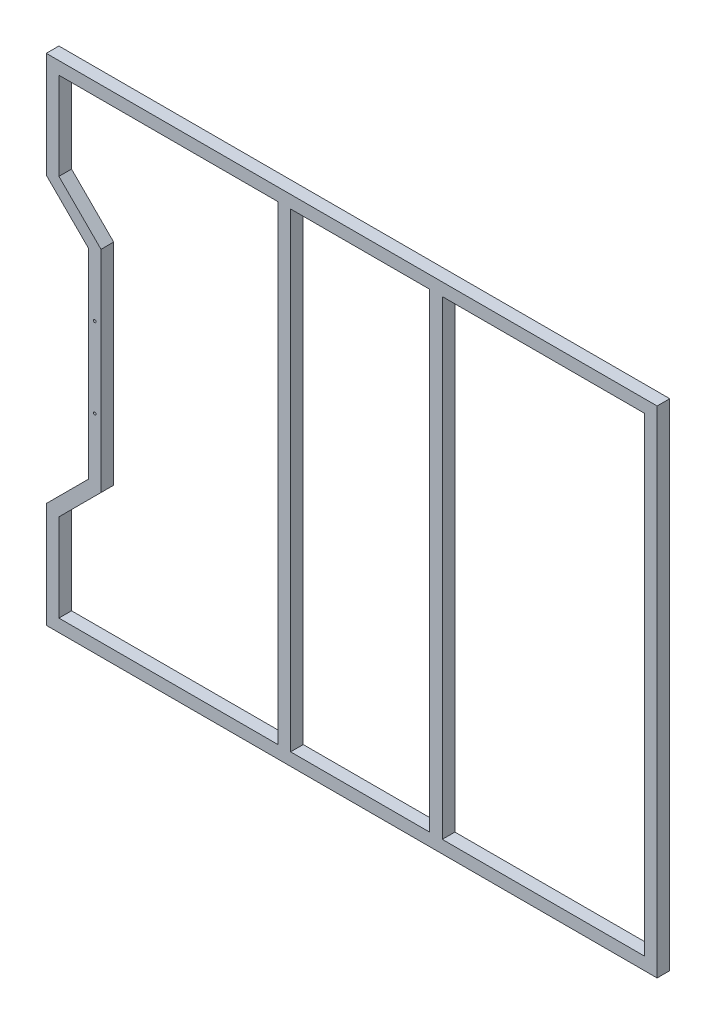
SolidWorks part; units mm, degrees
material "6061 合金"
ref_plane "前视基准面" through (0, 0, 0) normal (0, 0, 1) x (1, 0, 0)
ref_plane "上视基准面" through (0, 0, 0) normal (0, 1, 0) x (1, 0, 0)
ref_plane "右视基准面" through (0, 0, 0) normal (1, 0, 0) x (0, 0, -1)
sketch "草图2" plane through (0, 0, 324) normal (0, 0, 1) x (1, 0, 0)
  line L0 (-307.7002, 55) -> (-307.7002, 40)
  line L1 (-372.7002, 294) -> (352.3251, 294)
  line L2 (-372.7002, 294) -> (-372.7002, 295.2267)
  line L3 (-357.7002, 279) -> (-97.7002, 279)
  line L4 (352.3251, 294) -> (352.3251, 295)
  line L5 (-372.7002, 294) -> (-362.7002, 294)
  line L6 (-372.7002, 294) -> (-372.7002, 168.7868)
  line L8 (-357.7002, 279) -> (-357.7002, 175)
  line L10 (-372.7002, 168.7868) -> (-372.7002, 184.8427)
  line L18 (-322.7002, 40.0093) -> (-322.7002, 55)
  line L20 (352.3251, 40) -> (352.3251, 55)
  line L22 (352.3251, 40) -> (352.3251, 294)
  line L23 (352.3251, 294) -> (346.2002, 294)
  line L24 (337.3251, 55) -> (337.3251, 279)
  line L26 (97.3251, 55) -> (97.3251, 279)
  line L27 (147.5, 294) -> (132.5, 294)
  line L28 (82.3251, 55) -> (82.3251, 279)
  line L30 (-82.7002, 54.9596) -> (-82.7002, 279)
  line L31 (-132.5, 294) -> (-147.5, 294)
  line L32 (-97.7002, 54.9596) -> (-97.7002, 279)
  line L33 (-307.7002, -40) -> (-307.7002, -55)
  line L34 (-357.7002, 175) -> (-307.7002, 125)
  line L35 (-307.7002, 125) -> (-307.7002, 105)
  line L36 (-322.7002, 118.7868) -> (-372.7002, 168.7868)
  line L38 (-322.7002, 118.7868) -> (-322.7002, 40.0093)
  line L39 (-307.7002, 125) -> (-307.7002, 55)
  line L40 (-82.7002, 279) -> (82.3251, 279)
  line L41 (97.3251, 279) -> (337.3251, 279)
  line L44 (97.3251, -279) -> (337.3251, -279)
  line L45 (-82.7002, -279.0404) -> (82.3251, -279.0404)
  line L46 (-307.7002, -125) -> (-307.7002, -55)
  line L47 (-322.7002, -118.7868) -> (-322.7002, -40.0093)
  line L49 (-322.7002, -118.7868) -> (-372.7002, -168.7868)
  line L50 (-307.7002, -125) -> (-307.7002, -105)
  line L51 (-357.7002, -175) -> (-307.7002, -125)
  line L52 (-97.7002, 23.9878) -> (-97.7002, -279.0404)
  line L54 (-82.7002, -55.0404) -> (-82.7002, -279.0404)
  line L55 (-97.7002, 54.9596) -> (-97.7002, 39.9596)
  line L56 (82.3251, -55.0404) -> (82.3251, -279.0404)
  line L57 (147.5, -294) -> (132.5, -294)
  line L58 (97.3251, -55) -> (97.3251, -279)
  line L60 (337.3251, -55) -> (337.3251, -279)
  line L61 (352.3251, -294) -> (344.3251, -294)
  line L62 (352.3251, -40) -> (352.3251, -294)
  line L64 (352.3251, -40) -> (352.3251, -55)
  line L66 (-322.7002, -40.0093) -> (-322.7002, -55)
  line L68 (-372.7002, -168.7868) -> (-372.7002, -184.8427)
  line L70 (-357.7002, -279.0404) -> (-357.7002, -175)
  line L72 (-372.7002, -294) -> (-372.7002, -168.7868)
  line L74 (352.3251, -294) -> (352.3251, -295)
  line L75 (-357.7002, -279.0404) -> (-97.7002, -279.0404)
  line L77 (-372.7002, -294) -> (352.3251, -294)
  line L80 (-322.7002, 40.0093) -> (-322.7002, -40.0093)
  line L82 (-307.7002, 40) -> (-307.7002, -40)
  line L84 (-97.7002, 39.9596) -> (-97.7002, -40.0404)
  line L86 (-82.7002, 39.9596) -> (-82.7002, -40.0404)
  line L88 (82.3251, 40) -> (82.3251, -40)
  line L90 (97.3251, 40) -> (97.3251, -40)
  line L92 (337.3251, 40) -> (337.3251, -40)
  line L94 (352.3251, 40) -> (352.3251, -40)
  line L96 (-82.7002, 39.9596) -> (-82.7002, 54.9596)
  line L97 (-97.7002, 23.9878) -> (-97.7002, -40.0404)
  line L98 (-82.7002, -55.0404) -> (-82.7002, -40.0404)
  line L99 (82.3251, 55) -> (82.3251, 40)
  line L100 (97.3251, 40) -> (97.3251, 55)
  line L101 (82.3251, -40) -> (82.3251, -55.0404)
  line L102 (97.3251, -55) -> (97.3251, -40)
  line L103 (337.3251, 55) -> (337.3251, 40)
  line L104 (337.3251, -40) -> (337.3251, -55)
  line L105 (-332.7002, 55) -> (-332.7002, -55) construction
  point P28 (-357.7002, -279.0404)
  point P29 (-97.7002, -279.0404)
  dimension "D8" = 240
  dimension "D9" = 725.0253
  dimension "D12" = 15
  dimension "D1" = 15
  dimension "D2" = 15
  dimension "D3" = 15
  dimension "D4" = 15
  dimension "D5" = 50
  dimension "D6" = 260
  dimension "D7" = 15
  dimension "D10" = 40
  dimension "D13" = 15
  dimension "D16" = 15
  dimension "D19" = 135
extrude "凸台-拉伸1" add sketch "草图2" along normal blind 15 contours L94 L20 L22 L4 L1 L2 L6 L36 L38 L18 L80 L47 L49 L68 L72 L77 L57 L61 L62 L75 L70 L51 L46 L52 L26 region at (-367.7002, 284.6651, 324)
sketch "草图3" plane through (0, 0, 339) normal (0, 0, 1) x (1, 0, 0)
  circle A1 centre (-315.2002, 47.5) radius 1.6
  circle A21 centre (-315.2002, -47.5) radius 1.6
  point P8 (0, 0)
extrude "切除-拉伸1" cut sketch "草图3" against normal blind 15
